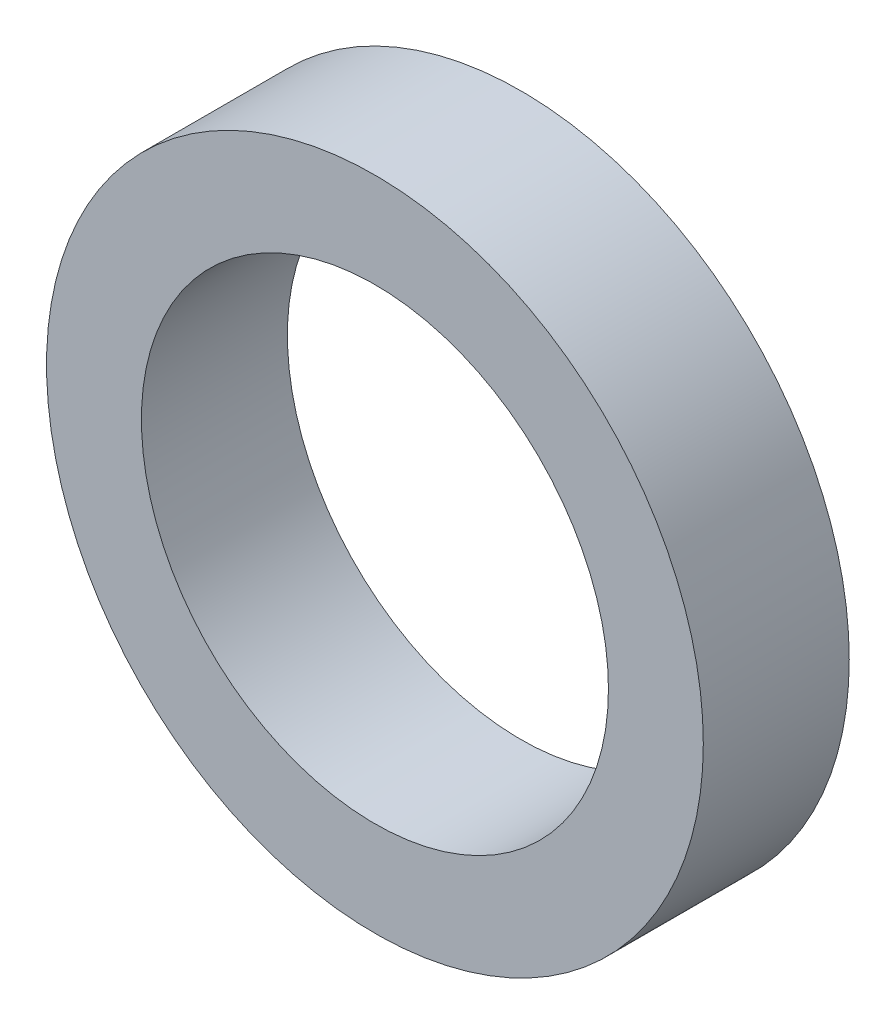
SolidWorks part; units mm, degrees
ref_plane "Front Plane" through (0, 0, 0) normal (0, 0, 1) x (1, 0, 0)
ref_plane "Top Plane" through (0, 0, 0) normal (0, 1, 0) x (1, 0, 0)
ref_plane "Right Plane" through (0, 0, 0) normal (1, 0, 0) x (0, 0, -1)
sketch "Sketch3" plane through (0, 0, 0) normal (0, 0, 1) x (1, 0, 0)
  circle A0 centre (0, 0) radius 1.6 construction
  circle A1 centre (0, 0) radius 2.25 construction
  point P6 (0, -1.6)
  dimension "OD" = 4.5
  dimension "ID" = 3.2
sketch "Sketch1" plane through (0, 0, 0) normal (1, 0, 0) x (0, 0, -1)
  line L0 (-0.5, -1.6) -> (-0.5, 1.6) construction
  line L1 (0.5, -2.25) -> (-0.5, -2.25) construction
  line L2 (0.5, -2.25) -> (0.5, 2.25) construction
  line L3 (0.5, 2.25) -> (-0.5, 2.25) construction
  line L4 (-0.5, -2.25) -> (-0.5, 2.25) construction
  line L5 (0, 2.25) -> (0, -2.25) construction
  line L6 (0.5, 0) -> (-0.5, 0) construction
  line L8 (0, 2.25) -> (0, -2.25) construction
  line L9 (-0.5, 1.6) -> (0, 1.6) construction
  point P0 (0, 0)
  point P7 (-0.5, 0)
  dimension "Length" = 1
sketch "Sketch2" plane through (0, 0, 0) normal (0, 0, 1) x (1, 0, 0)
  circle A0 centre (0, 0) radius 2.25
  circle A1 centre (0, 0) radius 1.6
extrude "Extrude1" add sketch "Sketch2" along normal up to vertex and the other way up to vertex up to point (0, -2.25, 0.5) other way up to point (0, 2.25, -0.5)
